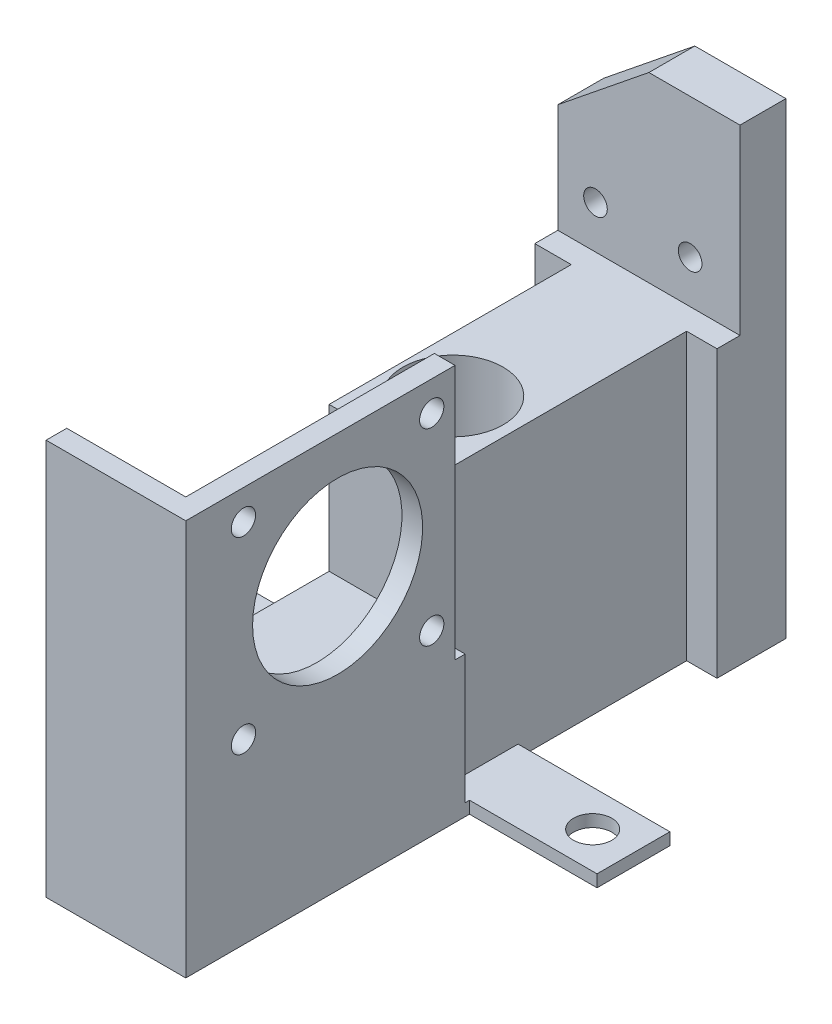
SolidWorks part; units mm, degrees
ref_plane "Front Plane" through (0, 0, 0) normal (0, 0, 1) x (1, 0, 0)
ref_plane "Top Plane" through (0, 0, 0) normal (0, 1, 0) x (1, 0, 0)
ref_plane "Right Plane" through (0, 0, 0) normal (1, 0, 0) x (0, 0, -1)
sketch "Sketch1" plane through (0, 0, 0) normal (0, 1, 0) x (1, 0, 0)
  line L0 (-48.7324, 38.4431) -> (21.2676, -31.5569) construction
  line L1 (-48.7324, 38.4431) -> (21.2676, 38.4431)
  line L2 (-48.7324, 38.4431) -> (-48.7324, -31.5569)
  line L4 (21.2676, 38.4431) -> (21.2676, -31.5569)
  line L5 (-48.7324, -31.5569) -> (21.2676, 38.4431) construction
  line L6 (-13.7324, 3.4431) -> (-13.7324, 29.4761) construction
  line L7 (-48.7324, -31.5569) -> (-48.7324, -79.8576)
  line L8 (-48.7324, -79.8576) -> (21.2676, -79.8576)
  line L9 (21.2676, -79.8576) -> (21.2676, -31.5569)
  circle A0 centre (-42.0166, 31.7274) radius 3.15
  circle A1 centre (14.5519, 31.7274) radius 3.15
  circle A2 centre (14.5519, -24.8412) radius 3.15
  circle A3 centre (-42.0166, -24.8412) radius 3.15
  circle A4 centre (-13.7324, -19.5569) radius 8.25
  point P6 (-13.7324, 3.4431)
  point P16 (-13.7324, 3.4431)
  dimension "D1" = 6.3
  dimension "D3" = 40
  dimension "D4" = 16.5
  dimension "D5" = 23
  dimension "D6" = 70
  dimension "D2" = 4
extrude "Boss-Extrude1" add sketch "Sketch1" along normal blind 2
sketch "Sketch2" plane through (0, 2, 0) normal (0, 1, 0) x (1, 0, 0)
  line L1 (-28.7324, 20.2631) -> (1.2676, 20.2631)
  line L2 (-28.7324, 20.2631) -> (-28.7324, 9.1031)
  line L5 (-13.7324, -36.2685) -> (-13.7324, 40.4624) construction
  line L6 (-48.7324, 38.4431) -> (-48.7324, -79.8576) construction
  line L7 (21.2676, -79.8576) -> (21.2676, 38.4431) construction
  line L10 (-22.7324, 12.2031) -> (-22.7324, -35.7969) construction
  line L11 (-22.7324, 5.9877) -> (-22.7324, -31.5569)
  line L12 (-22.7324, 8.8031) -> (-22.7324, -32.3969) construction
  line L15 (-22.7324, -31.5569) -> (-3.7324, -31.5569)
  line L34 (-22.7324, 8.9165) -> (-28.7324, 8.9165)
  line L41 (-28.7324, 8.9165) -> (-28.7324, 9.1031)
  line L42 (-22.7324, 8.9165) -> (-22.7324, 5.9877)
  line L43 (1.2676, 20.2631) -> (1.2676, 8.9165)
  line L44 (1.2676, 8.9165) -> (-3.7324, 8.9165)
  line L59 (-3.7324, 8.9165) -> (-3.7324, -31.5569)
  dimension "D1" = 30
extrude "Boss-Extrude2" add sketch "Sketch2" along normal blind 45
sketch "Sketch3" plane through (0, 2, 0) normal (0, -1, 0) x (1, 0, 0)
  circle A2 centre (-13.7324, 19.5569) radius 8.25
  circle A3 centre (-13.7324, 19.5569) radius 8.25
  dimension "D1" = 0
extrude "Cut-Extrude1" cut sketch "Sketch3" against normal through all
sketch "Sketch4" plane through (0, 47, 0) normal (0, 1, 0) x (1, 0, 0)
  line L0 (1.2676, 8.9165) -> (1.2676, 20.2631) construction
  line L3 (1.2676, 12.7031) -> (-28.7324, 12.7031)
  line L4 (1.2676, 12.7031) -> (1.2676, 20.2631)
  line L5 (1.2676, 20.2631) -> (-28.7324, 20.2631)
  line L6 (-28.7324, 12.7031) -> (-28.7324, 20.2631)
  line L8 (-25.7324, 12.2031) -> (-3.7324, 12.2031) construction
  dimension "D1" = 0.5
extrude "Boss-Extrude3" add sketch "Sketch4" along normal blind 30
sketch "Sketch5" plane through (0, 0, -12.7031) normal (0, 0, 1) x (1, 0, 0)
  circle A0 centre (-22.5274, 54.0695) radius 1.945
  circle A1 centre (-6.9374, 54.0695) radius 1.945
extrude "Cut-Extrude2" cut sketch "Sketch5" against normal through all
sketch "Sketch6" plane through (0, 2, 0) normal (0, 1, 0) x (1, 0, 0)
  line L0 (-48.7324, 38.4431) -> (-48.7324, -79.8576) construction
  line L10 (-22.7324, 8.9165) -> (-22.7324, -31.5569) construction
  line L28 (-48.7324, -18.8412) -> (-22.7324, -18.8412)
  line L29 (-3.7324, -18.8412) -> (21.2676, -18.8412)
  line L30 (-3.7324, -31.5569) -> (-3.7324, 8.9165) construction
  line L31 (21.2676, -79.8576) -> (21.2676, 38.4431) construction
  line L79 (-22.7324, 8.9165) -> (-22.7324, -31.5569)
  line L80 (-22.7324, 8.9165) -> (-22.7324, -18.8412)
  line L82 (-28.7324, 8.9165) -> (-22.7324, 8.9165)
  line L83 (-28.7324, 8.9165) -> (-22.7324, 8.9165)
  line L85 (-28.7324, 12.7031) -> (-28.7324, 8.9165)
  line L86 (-28.7324, 12.7031) -> (-28.7324, 8.9165)
  line L95 (1.2676, 12.7031) -> (1.2676, 20.2631)
  line L96 (1.2676, 20.2631) -> (-28.7324, 20.2631)
  line L97 (-28.7324, 20.2631) -> (-28.7324, 12.7031)
  line L98 (1.2676, 8.9165) -> (1.2676, 20.2631)
  line L99 (1.2676, 20.2631) -> (-28.7324, 20.2631)
  line L100 (-28.7324, 20.2631) -> (-28.7324, 12.7031)
  line L101 (1.2676, 8.9165) -> (1.2676, 20.2631)
  line L105 (-3.7324, -31.5569) -> (-3.7324, 8.9165)
  line L106 (-3.7324, 8.9165) -> (1.2676, 8.9165)
  line L107 (-3.7324, -18.8412) -> (-3.7324, 8.9165)
  line L108 (-3.7324, 8.9165) -> (1.2676, 8.9165)
  line L110 (-48.7324, -30.8412) -> (-44.9403, -30.8412)
  line L111 (0.2676, -30.8412) -> (21.2676, -30.8412)
  line L113 (21.2676, -79.8576) -> (21.2676, 38.4431)
  line L114 (21.2676, 38.4431) -> (-48.7324, 38.4431)
  line L115 (-48.7324, 38.4431) -> (-48.7324, -79.8576)
  line L116 (21.2676, -18.8412) -> (21.2676, 38.4431)
  line L117 (21.2676, 38.4431) -> (-48.7324, 38.4431)
  line L118 (-48.7324, 38.4431) -> (-48.7324, -18.8412)
  line L119 (-44.9403, -30.8412) -> (-44.9403, -77.5569)
  line L120 (-44.9403, -77.5569) -> (0.2676, -77.5569)
  line L121 (0.2676, -77.5569) -> (0.2676, -30.8412)
  line L122 (-48.7324, -30.8412) -> (-48.7324, -79.8576)
  line L123 (-48.7324, -79.8576) -> (21.2676, -79.8576)
  line L124 (21.2676, -79.8576) -> (21.2676, -30.8412)
  line L125 (-4.2324, -73.5569) -> (-42.7324, -73.5569) construction
  line L126 (-3.7324, -36.7995) -> (-3.7324, -68.3143) construction
  circle A0 centre (-42.0166, -24.8412) radius 3.15 construction
  dimension "D1" = 6
  dimension "D9" = 6
  dimension "D10" = 4
  dimension "D11" = 4
  dimension "D2" = 0
  dimension "D3" = 0
  dimension "D4" = 0
  dimension "D5" = 0
  dimension "D6" = 0
  dimension "D7" = 0
  dimension "D8" = 0
extrude "Cut-Extrude3" cut sketch "Sketch6" against normal through all
sketch "Sketch10" plane through (0, 2, 0) normal (0, 1, 0) x (1, 0, 0)
  line L0 (0.2676, -77.5569) -> (-44.9403, -77.5569) construction
  line L1 (0.2676, -77.5569) -> (-22.7324, -77.5569)
  line L2 (0.2676, -77.5569) -> (0.2676, -31.5569)
  line L3 (0.2676, -31.5569) -> (-22.7324, -31.5569)
  line L4 (-22.7324, -77.5569) -> (-22.7324, -31.5569)
  line L5 (0.2676, -30.8412) -> (0.2676, -77.5569) construction
extrude "Boss-Extrude4" add sketch "Sketch10" along normal blind 21.2
sketch "Sketch11" plane through (0, 2, 0) normal (0, 1, 0) x (1, 0, 0)
  line L1 (-44.9403, -30.8412) -> (-22.7324, -30.8412)
  line L2 (-44.9403, -30.8412) -> (-44.9403, -77.5569)
  line L3 (-44.9403, -77.5569) -> (-22.7324, -77.5569)
  line L4 (-22.7324, -30.8412) -> (-22.7324, -77.5569)
extrude "Cut-Extrude4" cut sketch "Sketch11" against normal through all
sketch "Sketch12" plane through (-22.7324, 0, 0) normal (-1, 0, 0) x (0, 0, 1)
  line L0 (-8.9165, 47) -> (31.5569, 47) construction
  line L1 (31.5569, 23.2) -> (30.9569, 23.2)
  line L2 (31.5569, 23.2) -> (31.5569, 47)
  line L3 (31.5569, 47) -> (30.9569, 47)
  line L4 (30.9569, 23.2) -> (30.9569, 47)
  dimension "D1" = 0.6
extrude "Cut-Extrude5" cut sketch "Sketch12" against normal through all
sketch "Sketch13" plane through (0, 23.2, 0) normal (0, 1, 0) x (1, 0, 0)
  line L0 (-22.7324, -30.9569) -> (-22.7324, -77.5569) construction
  line L1 (0.2676, -77.5569) -> (-22.7324, -77.5569)
  line L2 (0.2676, -77.5569) -> (0.2676, -74.1569)
  line L3 (-3.1324, -74.1569) -> (-22.7324, -74.1569)
  line L4 (-22.7324, -77.5569) -> (-22.7324, -74.1569)
  line L5 (-4.2324, -73.5569) -> (-42.7324, -73.5569) construction
  line L7 (0.2676, -74.1569) -> (0.2676, -33.2235)
  line L8 (0.2676, -33.2235) -> (-3.1324, -33.2235)
  line L9 (-3.1324, -74.1569) -> (-3.1324, -33.2235)
  line L10 (-3.7324, -36.7995) -> (-3.7324, -68.3143) construction
  dimension "D1" = 0.6
  dimension "D2" = 0.6
extrude "Boss-Extrude5" add sketch "Sketch13" along normal blind 42
sketch "Sketch14" plane through (-3.1324, 0, 0) normal (-1, 0, 0) x (0, 0, 1)
  circle A0 centre (52.5569, 44.7853) radius 14
  dimension "D1" = 28
extrude "Cut-Extrude6" cut sketch "Sketch14" against normal through all
sketch "Sketch15" plane through (-3.1324, 0, 0) normal (-1, 0, 0) x (0, 0, 1)
  circle A0 centre (68.0569, 29.2853) radius 2
  circle A1 centre (37.0569, 29.2853) radius 2
  circle A2 centre (37.0569, 60.2853) radius 2
  circle A4 centre (68.0569, 60.2853) radius 2
  dimension "D1" = 4
extrude "Cut-Extrude7" cut sketch "Sketch15" against normal through all
sketch "Sketch16" plane through (0, 0, -20.2631) normal (0, 0, -1) x (-1, 0, 0)
  line L0 (28.7324, 64.9066) -> (13.7324, 77)
  line L1 (28.7324, 77) -> (28.7324, 0) construction
  line L2 (42.7324, 64.9066) -> (4.2324, 64.9066) construction
  line L3 (-1.2676, 77) -> (28.7324, 77) construction
  line L4 (13.7324, 77) -> (28.7324, 77)
  line L5 (28.7324, 77) -> (28.7324, 64.9066)
extrude "Cut-Extrude8" cut sketch "Sketch16" against normal through all
sketch "Sketch17" plane through (0, 77, 0) normal (0, 1, 0) x (1, 0, 0)
  line L8 (-13.7324, 20.2631) -> (-13.7324, 12.7031)
  line L9 (-13.7324, 12.7031) -> (1.2676, 12.7031)
  line L10 (1.2676, 12.7031) -> (1.2676, 20.2631)
  line L11 (1.2676, 20.2631) -> (-13.7324, 20.2631)
  line L12 (-13.7324, 20.2631) -> (-13.7324, 12.7031)
  line L13 (-13.7324, 12.7031) -> (1.2676, 12.7031)
  line L14 (1.2676, 12.7031) -> (1.2676, 20.2631)
  line L15 (1.2676, 20.2631) -> (-13.7324, 20.2631)
  dimension "D1" = 0
